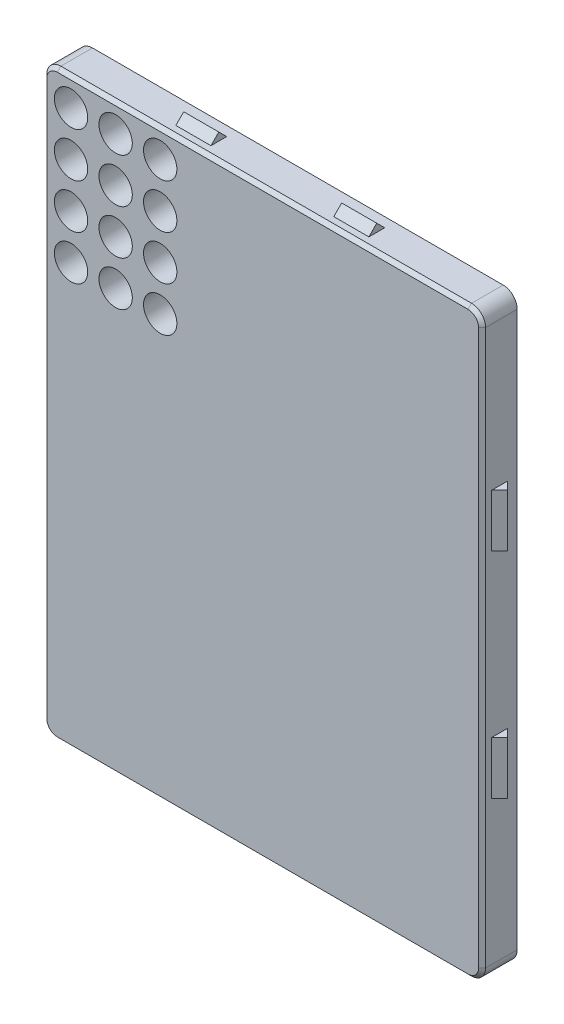
SolidWorks part; units mm, degrees
ref_plane "前视基准面" through (0, 0, 0) normal (0, 0, 1) x (1, 0, 0)
ref_plane "上视基准面" through (0, 0, 0) normal (0, 1, 0) x (1, 0, 0)
ref_plane "右视基准面" through (0, 0, 0) normal (1, 0, 0) x (0, 0, -1)
sketch "草图1" plane through (0, 0, 0) normal (0, 0, 1) x (1, 0, 0)
  line L1 (12.5, -16.6) -> (-12.5, -16.6)
  line L2 (12.5, -16.6) -> (12.5, 16.6)
  line L3 (12.5, 16.6) -> (-12.5, 16.6)
  line L4 (-12.5, -16.6) -> (-12.5, 16.6)
  line L5 (12.5, -16.6) -> (-12.5, 16.6) construction
  line L6 (12.5, 16.6) -> (-12.5, -16.6) construction
  point P0 (0, 0)
  dimension "D1" = 25
  dimension "D2" = 33.2
extrude "凸台-拉伸1" add sketch "草图1" along normal blind 2
fillet "圆角1" radius 0.8 4 edges at (12.5, -16.6, 1) (-12.5, -16.6, 1) (-12.5, 16.6, 1) (12.5, 16.6, 1)
chamfer "倒角1" distance 0.2 angle 45 8 edges at (-12.5, 0, 2) (-12.2657, -16.3657, 2) (-12.2657, 16.3657, 2) (0, -16.6, 2) (0, 16.6, 2) (12.2657, -16.3657, 2) (12.2657, 16.3657, 2) (12.5, 0, 2)
sketch "草图3" plane through (0, 0, 0) normal (0, 0, -1) x (-1, 0, 0)
  line L0 (12.5, 15.8) -> (12.5, -15.8) construction
  line L1 (-11.7, 16.6) -> (11.7, 16.6) construction
  circle A0 centre (10.92, 15.02) radius 0.95
  circle A1 centre (8.38, 15.02) radius 0.95
  circle A2 centre (5.84, 15.02) radius 0.95
  circle A3 centre (8.38, 12.48) radius 0.95
  circle A4 centre (5.84, 12.48) radius 0.95
  circle A5 centre (8.38, 9.94) radius 0.95
  circle A6 centre (5.84, 9.94) radius 0.95
  circle A7 centre (8.38, 7.4) radius 0.95
  circle A8 centre (5.84, 7.4) radius 0.95
  circle A9 centre (10.92, 12.48) radius 0.95
  circle A10 centre (10.92, 9.94) radius 0.95
  circle A11 centre (10.92, 7.4) radius 0.95
  dimension "D1" = 1.9
  dimension "D2" = 1.58
  dimension "D3" = 1.58
  dimension "D4" = 3
  dimension "D5" = 4
extrude "切除-拉伸2" cut sketch "草图3" against normal through all
sketch "草图4" plane through (0, -16.6, 0) normal (0, -1, 0) x (1, 0, 0)
  line L0 (12.5, 1.45) -> (12.95, 1)
  line L1 (12.5, 1.8) -> (12.5, 0) construction
  line L2 (12.95, 1) -> (12.5, 0.55)
  line L3 (12.5, 1.45) -> (12.5, 0.55)
  line L4 (-11.7, 2) -> (11.7, 2) construction
  line L5 (-11.7, 0) -> (11.7, 0) construction
  line L6 (0, 3.8012) -> (0, -2.3615) construction
  line L7 (-12.5, 1.45) -> (-12.95, 1)
  line L8 (-12.95, 1) -> (-12.5, 0.55)
  line L9 (-12.5, 1.45) -> (-12.5, 0.55)
  dimension "D1" = 0.55
  dimension "D2" = 0.55
  dimension "D3" = 90
  dimension "D4" = 45
extrude "凸台-拉伸2" add sketch "草图4" against normal up to surface (33.2 mm away) up to face at (0, 16.6, 0.9)
sketch "草图5" plane through (0, 0, 2) normal (0, 0, 1) x (1, 0, 0)
  line L0 (-12.95, 16.6) -> (-12.95, -16.6) construction
  line L1 (-12.5, 16.6) -> (-12.95, 16.6)
  line L2 (-12.5, 16.6) -> (-12.5, 7.6)
  line L3 (-12.5, 7.6) -> (-12.95, 7.6)
  line L4 (-12.95, 16.6) -> (-12.95, 7.6)
  line L5 (-12.5, -15.8) -> (-12.5, 15.8) construction
  line L6 (-12.95, 4.6) -> (-12.5, 4.6)
  line L7 (-12.95, 4.6) -> (-12.95, -4.6)
  line L8 (-12.95, -4.6) -> (-12.5, -4.6)
  line L9 (-12.5, 4.6) -> (-12.5, -4.6)
  line L10 (0, -1000) -> (0, 49000) construction
  line L11 (-12.5, -16.6) -> (-12.95, -16.6)
  line L12 (-12.5, -16.6) -> (-12.5, -7.6)
  line L13 (-12.5, -7.6) -> (-12.95, -7.6)
  line L14 (-12.95, -16.6) -> (-12.95, -7.6)
  line L15 (12.5, -7.6) -> (12.95, -7.6)
  line L16 (12.95, -16.6) -> (12.95, -7.6)
  line L17 (12.5, -16.6) -> (12.95, -16.6)
  line L18 (12.5, -16.6) -> (12.5, -7.6)
  line L19 (12.95, -4.6) -> (12.5, -4.6)
  line L20 (12.95, 4.6) -> (12.5, 4.6)
  line L21 (12.95, 4.6) -> (12.95, -4.6)
  line L22 (12.5, 4.6) -> (12.5, -4.6)
  line L23 (12.5, 7.6) -> (12.95, 7.6)
  line L24 (12.95, 16.6) -> (12.95, 7.6)
  line L25 (12.5, 16.6) -> (12.95, 16.6)
  line L26 (12.5, 16.6) -> (12.5, 7.6)
  point P18 (-12.725, 4.6)
  dimension "D1" = 9
  dimension "D2" = 3
  dimension "D3" = 9
  dimension "D4" = 3
extrude "切除-拉伸3" cut sketch "草图5" against normal through all both and the other way through all
sketch "草图6" plane through (12.5, 0, 0) normal (1, 0, 0) x (0, 0, -1)
  line L0 (-1.45, 16.6) -> (-0.55, 16.6)
  line L1 (-1.8, 16.6) -> (0, 16.6) construction
  line L2 (-0.55, 16.6) -> (-1, 17.05)
  line L3 (-1, 17.05) -> (-1.45, 16.6)
  line L4 (-2, -15.8) -> (-2, 15.8) construction
  line L5 (0, -15.8) -> (0, 15.8) construction
  line L6 (-1000, 0) -> (49000, 0) construction
  line L7 (-0.55, -16.6) -> (-1, -17.05)
  line L8 (-1.45, -16.6) -> (-0.55, -16.6)
  line L9 (-1, -17.05) -> (-1.45, -16.6)
  dimension "D1" = 0.55
  dimension "D2" = 0.55
  dimension "D3" = 90
  dimension "D4" = 45
extrude "凸台-拉伸3" add sketch "草图6" against normal up to surface (25 mm away) up to face at (-12.5, -6.1, 1)
sketch "草图7" plane through (0, 0, 2) normal (0, 0, 1) x (1, 0, 0)
  line L0 (-1000, 0) -> (49000, 0) construction
  line L1 (-11.7, 16.6) -> (11.7, 16.6) construction
  line L2 (-12.5, 17.05) -> (-5.5, 17.05)
  line L3 (-12.5, 17.05) -> (-12.5, 16.6)
  line L4 (-12.5, 16.6) -> (-5.5, 16.6)
  line L5 (-5.5, 17.05) -> (-5.5, 16.6)
  line L6 (-12.5, 17.05) -> (12.5, 17.05) construction
  line L7 (-3.5, 17.05) -> (3.5, 17.05)
  line L8 (-3.5, 17.05) -> (-3.5, 16.6)
  line L9 (-3.5, 16.6) -> (3.5, 16.6)
  line L10 (3.5, 17.05) -> (3.5, 16.6)
  line L11 (-11.7, 16.6) -> (11.7, 16.6) construction
  line L12 (12.5, -16.6) -> (5.5, -16.6)
  line L13 (12.5, 17.05) -> (5.5, 17.05)
  line L14 (12.5, 17.05) -> (12.5, 16.6)
  line L15 (12.5, 16.6) -> (5.5, 16.6)
  line L16 (5.5, 17.05) -> (5.5, 16.6)
  line L17 (5.5, -17.05) -> (5.5, -16.6)
  line L18 (12.5, -17.05) -> (5.5, -17.05)
  line L19 (12.5, -17.05) -> (12.5, -16.6)
  line L20 (-3.5, -16.6) -> (3.5, -16.6)
  line L21 (3.5, -17.05) -> (3.5, -16.6)
  line L22 (-3.5, -17.05) -> (3.5, -17.05)
  line L23 (-3.5, -17.05) -> (-3.5, -16.6)
  line L24 (-12.5, -16.6) -> (-5.5, -16.6)
  line L25 (-5.5, -17.05) -> (-5.5, -16.6)
  line L26 (-12.5, -17.05) -> (-5.5, -17.05)
  line L27 (-12.5, -17.05) -> (-12.5, -16.6)
  dimension "D1" = 7
  dimension "D2" = 2
  dimension "D3" = 2
  dimension "D4" = 7
extrude "切除-拉伸4" cut sketch "草图7" against normal through all both and the other way through all
